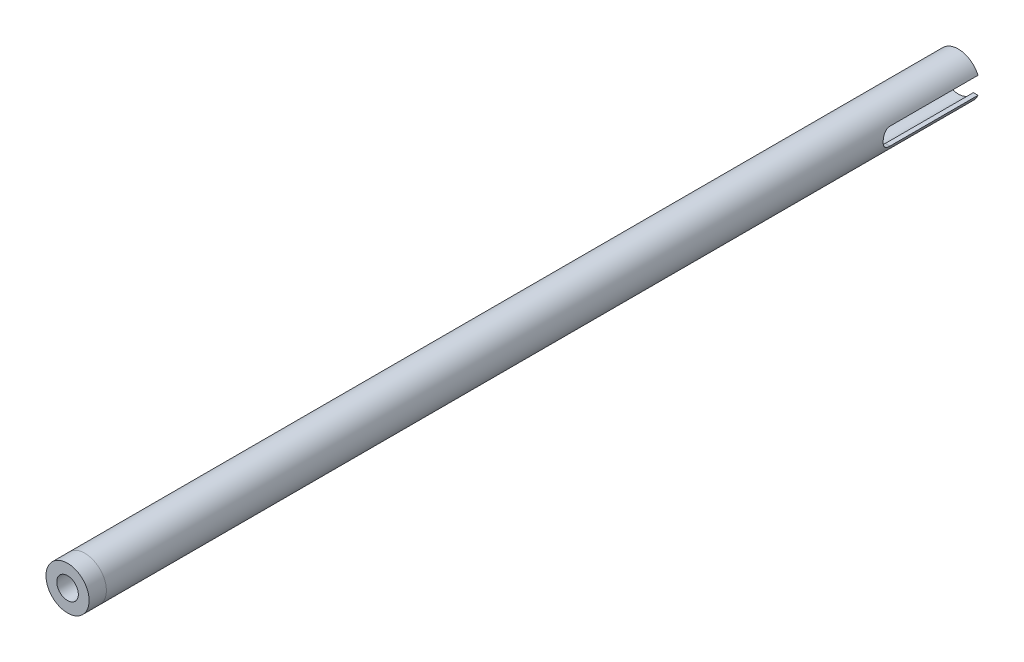
SolidWorks part; units mm, degrees
material "AISI 4130 Steel, annealed at 865C"
ref_plane "Front Plane" through (0, 0, 0) normal (0, 0, 1) x (1, 0, 0)
ref_plane "Top Plane" through (0, 0, 0) normal (0, 1, 0) x (1, 0, 0)
ref_plane "Right Plane" through (0, 0, 0) normal (1, 0, 0) x (0, 0, -1)
sketch "Axis" plane through (0, 0, 0) normal (0, 1, 0) x (1, 0, 0)
  line L0 (0, 0) -> (0, 327.5709) construction
  line L1 (0, 0) -> (0, -28.575) construction
  line L2 (0, 327.5709) -> (-7.9375, 327.5709) construction
  line L4 (0, 355.931) -> (-26.4723, 261.3474) construction
  dimension "D1" = 28.575
  dimension "D2" = 7.9375
sketch "Sketch1" plane through (0, 0, 0) normal (0, 0, 1) x (1, 0, 0)
  line L0 (-7.9375, 0) -> (7.9375, 0) construction
  line L1 (-7.2748, 3.175) -> (7.2748, 3.175)
  line L2 (-7.2748, -3.175) -> (7.2748, -3.175)
  circle A0 centre (0, 0) radius 7.9375
  circle A1 centre (0, 0) radius 6.4135
  circle A2 centre (0, 0) radius 3.9688
  dimension "D1" = 15.875
  dimension "D3" = 7.9375
  dimension "D2" = 1.524
  dimension "D4" = 6.35
extrude "Threaded insert 1-1" add sketch "Sketch1" against normal blind 6.35 contours A2 L1 A1 | A1 L1 A0 | A2 L0 A1 L1 | A1 L0 A0 L1 | L0 A1 L2 A0 | L0 A2 L2 A1 | A2 L2 A1 | A1 L2 A0 | L0 A1 L2 A2 | L0 A0 L2 A1 | A0 L0 A1 L1 | A1 L0 A2 L1 region at (4.7887, 1.6543, 0) region at (4.7887, -1.6543, 0) region at (6.9234, 1.6163, 0) region at (6.9234, -1.6163, 0) region at (-4.7887, -1.6543, 0) region at (-4.7887, 1.6543, 0) region at (0, 4.6159, 0) region at (0, -4.6159, 0) region at (0, 6.5666, 0) region at (6.4237, -3.3281, 0) region at (-6.9234, -1.6163, 0) region at (-6.9234, 1.6163, 0)
extrude "Threaded insert 1-2" add sketch "Sketch1<3>" against normal blind 9.525 from surface contours A2 L1 A1 | A2 L0 A1 L1 | L0 A2 L2 A1 | A2 L2 A1 | L0 A1 L2 A2 | A1 L0 A2 L1 region at (4.7887, 1.6543, 0) region at (4.7887, -1.6543, 0) region at (-4.7887, -1.6543, 0) region at (-4.7887, 1.6543, 0) region at (0, 4.6159, 0) region at (0, -4.6159, 0) starting at face at (7.9375, 0, -6.35)
sketch "Sketch1<3>" plane through (0, 0, 0) normal (0, 0, 1) x (1, 0, 0) same geometry as "Sketch1"
extrude "A-arm tube" add sketch "Sketch1<4>" against normal up to vertex (327.5709 mm away) from surface separate body contours A1 L1 A0 | A1 L0 A0 L1 | L0 A1 L2 A0 | A1 L2 A0 | L0 A0 L2 A1 | A0 L0 A1 L1 region at (6.9234, 1.6163, 0) region at (6.9234, -1.6163, 0) region at (0, 6.5666, 0) region at (6.4237, -3.3281, 0) region at (-6.9234, -1.6163, 0) region at (-6.9234, 1.6163, 0) up to point (0, 0, -327.5709) starting at face at (6.4135, 0, -6.35)
sketch "Sketch1<4>" plane through (0, 0, 0) normal (0, 0, 1) x (1, 0, 0) same geometry as "Sketch1"
extrude "Apex slot" cut sketch "Sketch1<5>" along normal blind 35.56 from surface contours A0 L0 A1 L1 | L0 A0 L2 A1 | A1 L0 A0 L1 | L0 A1 L2 A0 region at (6.9234, 1.6163, 0) region at (6.9234, -1.6163, 0) region at (-6.9234, -1.6163, 0) region at (-6.9234, 1.6163, 0) starting at face at (6.4135, 0, -327.5709)
sketch "Sketch1<5>" plane through (0, 0, 0) normal (0, 0, 1) x (1, 0, 0) same geometry as "Sketch1"
fillet "Fillet1" radius 3.175 4 edges at (-6.4237, 3.175, -292.0109) (-6.4237, -3.175, -292.0109) (6.4237, -3.175, -292.0109) (6.4237, 3.175, -292.0109)
equation "\"tube diameter\"= 5 / 8"
equation "\"tube thickness\"= .06"
equation "\"apex thickness\"= .25"
equation "\"tube slot\"= 1.4"
equation "\"D1@Sketch1\"=\"tube diameter\""
equation "\"D2@Sketch1\"=\"tube thickness\""
equation "\"threaded insert hole\"= .3125"
equation "\"D3@Sketch1\"=\"threaded insert hole\""
equation "\"D4@Sketch1\"=\"apex thickness\""
equation "\"D1@Apex slot\" = \"tube slot\""
equation "\"D1@Fillet1\"=\"apex thickness\"/2"
equation "\"D2@Axis\"=\"tube diameter\"/2"
